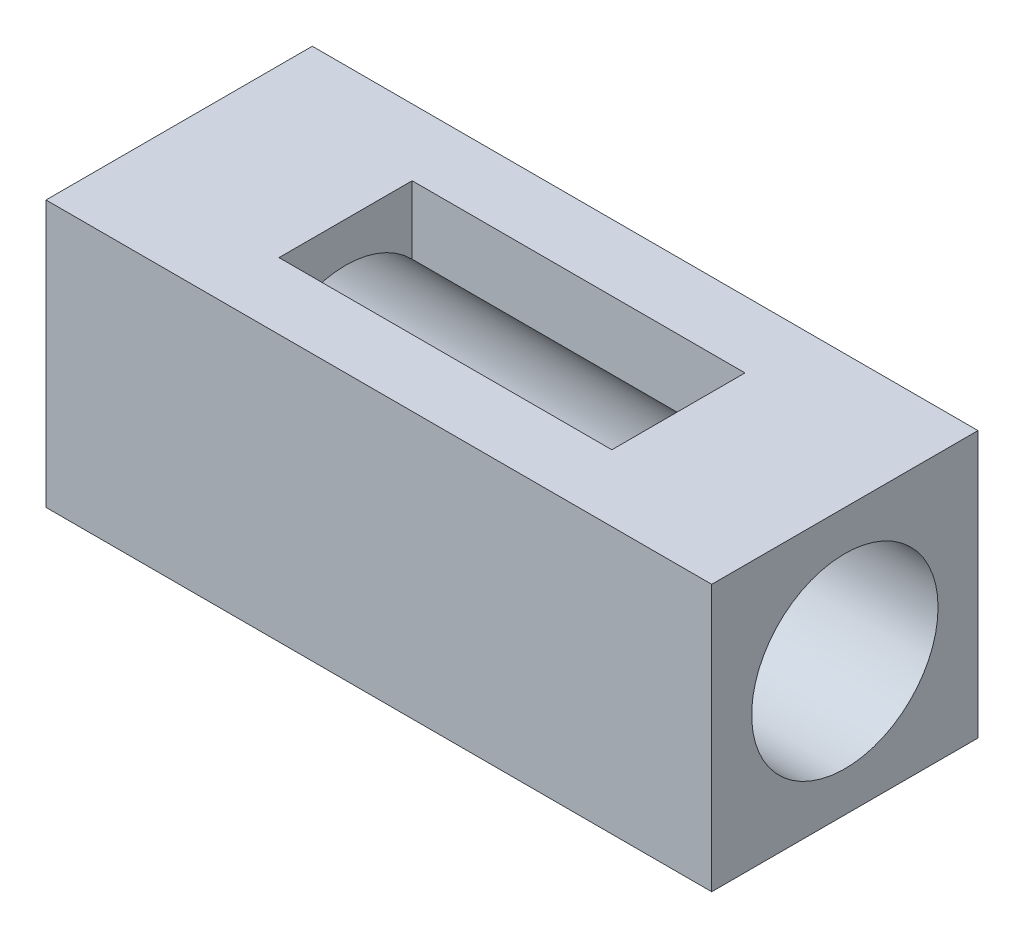
SolidWorks part; units mm, degrees
ref_plane "Alzado" through (0, 0, 0) normal (0, 0, 1) x (1, 0, 0)
ref_plane "Planta" through (0, 0, 0) normal (0, 1, 0) x (1, 0, 0)
ref_plane "Vista lateral" through (0, 0, 0) normal (1, 0, 0) x (0, 0, -1)
sketch "Croquis1" plane through (0, 0, 0) normal (0, 0, 1) x (1, 0, 0)
  line L1 (0, 0) -> (1000, 0)
  line L2 (0, 0) -> (0, 400)
  line L3 (0, 400) -> (1000, 400)
  line L4 (1000, 0) -> (1000, 400)
  dimension "D1" = 400
  dimension "D2" = 1000
extrude "Saliente-Extruir1" add sketch "Croquis1" along normal blind 400
sketch "Croquis2" plane through (1000, 0, 0) normal (1, 0, 0) x (0, 0, -1)
  line L0 (-400, 0) -> (-400, 400) construction
  line L1 (-400, 400) -> (0, 400) construction
  circle A0 centre (-200, 200) radius 140
  point P4 (0, 0)
  point P5 (0, 0)
  point P6 (0, 0)
  dimension "D1" = 200
  dimension "D2" = 200
extrude "Cortar-Extruir1" cut sketch "Croquis2" against normal blind 1000 contours A0
sketch "Croquis3" plane through (0, 0, 0) normal (0, -1, 0) x (1, 0, 0)
  line L0 (0, 400) -> (0, 0) construction
  line L1 (250, 300) -> (750, 300)
  line L2 (250, 300) -> (250, 100)
  line L3 (250, 100) -> (750, 100)
  line L4 (750, 300) -> (750, 100)
  line L5 (0, 0) -> (1000, 0) construction
  dimension "D1" = 500
  dimension "D2" = 200
  dimension "D3" = 250
  dimension "D4" = 100
extrude "Cortar-Extruir2" cut sketch "Croquis3" against normal blind 400
